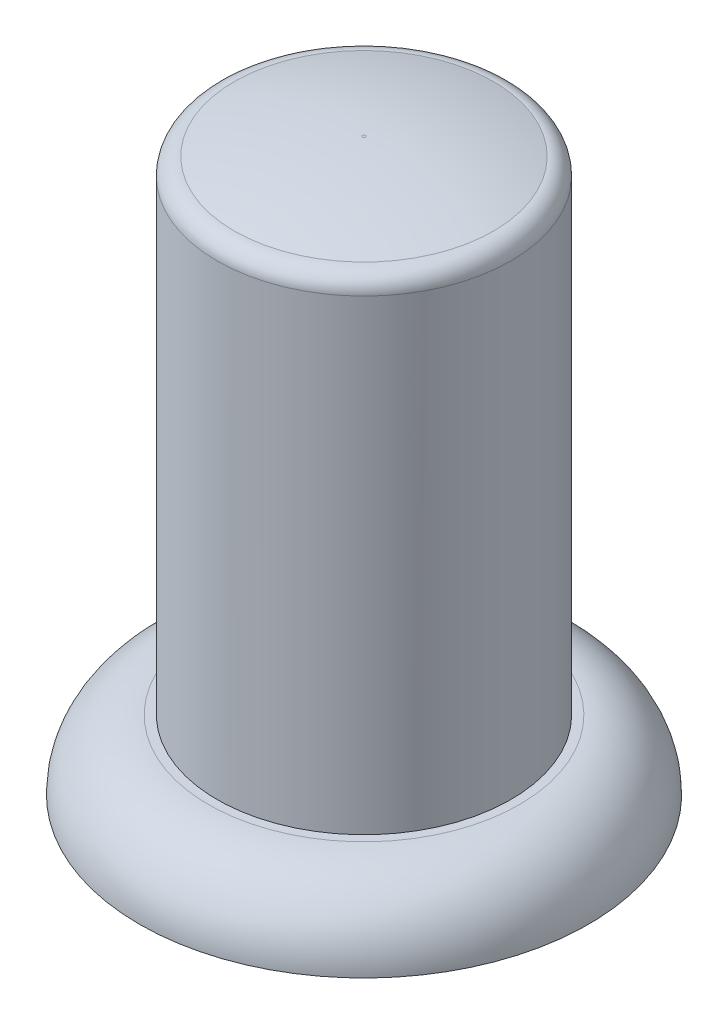
SolidWorks part; units mm, degrees
ref_plane "Front Plane" through (0, 0, 0) normal (0, 0, 1) x (1, 0, 0)
ref_plane "Top Plane" through (0, 0, 0) normal (0, 1, 0) x (1, 0, 0)
ref_plane "Right Plane" through (0, 0, 0) normal (1, 0, 0) x (0, 0, -1)
sketch "Sketch1" plane through (0, 0, 0) normal (0, 1, 0) x (1, 0, 0)
  circle A0 centre (0, 0) radius 4.25
  dimension "D1" = 8.5
extrude "Boss-Extrude1" add sketch "Sketch1" along normal blind 16
fillet "Fillet1" radius 0.5 1 edges at (0, 16, 4.25)
sketch "Sketch3" plane through (0, 16, 0) normal (0, 1, 0) x (1, 0, 0)
  circle A0 centre (0, 0) radius 3.75
  circle A1 centre (0, 0) radius 3.75 construction
extrude "Boss-Extrude3" add sketch "Sketch3" along normal blind 0.5
fillet "Fillet2" radius 14 1 edges at (0, 16.5, 3.75)
sketch "Sketch5" plane through (0, 0, 0) normal (0, -1, 0) x (1, 0, 0)
  circle A0 centre (0, 0) radius 3.5
  dimension "D1" = 7
extrude "Cut-Extrude1" cut sketch "Sketch5" against normal blind 5
sketch "Sketch6" plane through (0, 5, 0) normal (0, -1, 0) x (1, 0, 0)
  circle A0 centre (0, 0) radius 3
  dimension "D1" = 6
extrude "Cut-Extrude2" cut sketch "Sketch6" against normal blind 10
sketch "Sketch7" plane through (0, 15, 0) normal (0, -1, 0) x (1, 0, 0)
  line L0 (-3, 0) -> (3, 0) construction
  line L1 (1.5, -2.5981) -> (3, -2.5981)
  line L2 (1.5, -2.5981) -> (1.5, 2.5981)
  line L3 (1.5, 2.5981) -> (3, 2.5981)
  line L4 (3, -2.5981) -> (3, 2.5981)
  line L5 (1.5, -2.5981) -> (3, 2.5981) construction
  line L6 (1.5, 2.5981) -> (3, -2.5981) construction
  circle A0 centre (0, 0) radius 3 construction
  circle A1 centre (0, 0) radius 3 construction
  point P0 (2.25, 0)
  point P12 (1.5, 0)
  dimension "D1" = 4.5
extrude "Boss-Extrude5" add sketch "Sketch7" along normal blind 10
sketch "Sketch8" plane through (0, 0, 0) normal (0, -1, 0) x (1, 0, 0)
  circle A0 centre (0, 0) radius 6.5
  dimension "D1" = 13
extrude "Boss-Extrude6" add sketch "Sketch8" against normal blind 2
sketch "Sketch9" plane through (0, 0, 0) normal (0, -1, 0) x (1, 0, 0)
  circle A0 centre (0, 0) radius 3.5
  dimension "D1" = 7
extrude "Cut-Extrude3" cut sketch "Sketch9" against normal up to surface (2 mm away) up to face at (0, 2, -6.5)
fillet "Fillet3" radius 2 1 edges at (0, 2, -6.5)
